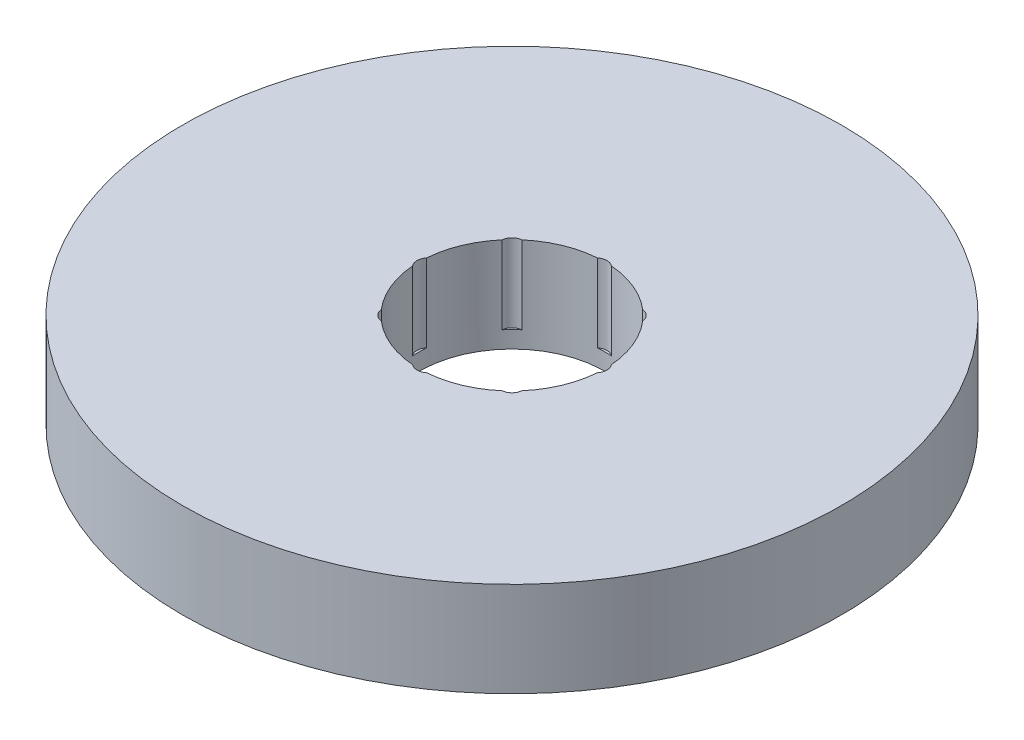
SolidWorks part; units mm, degrees
ref_plane "Front Plane" through (0, 0, 0) normal (0, 0, 1) x (1, 0, 0)
ref_plane "Top Plane" through (0, 0, 0) normal (0, 1, 0) x (1, 0, 0)
ref_plane "Right Plane" through (0, 0, 0) normal (1, 0, 0) x (0, 0, -1)
sketch "Sketch1" plane through (0, 0, 0) normal (0, 1, 0) x (1, 0, 0)
  circle A0 centre (0, 0) radius 80
  dimension "FLANGE_OD" = 160
extrude "Boss-Extrude1" add sketch "Sketch1" along normal blind 23
sketch "Sketch2" plane through (0, 0, 0) normal (0, 1, 0) x (1, 0, 0)
  circle A0 centre (0, 0) radius 22.5
  dimension "BORE_D" = 45
extrude "Cut-Extrude1" cut sketch "Sketch2" along normal through all
sketch "Sketch3" plane through (0, 23, 0) normal (0, 1, 0) x (1, 0, 0)
  circle A0 centre (0, 0) radius 20.3536 construction
  circle A1 centre (-20.3536, 0) radius 2.6855
  dimension "BOLT_D" = 5.371
  dimension "BOLT_PCD" = 40.7072
extrude "Cut-Extrude2" cut sketch "Sketch3" against normal blind 18.9106
pattern_circular "CirPattern1" count 8 over 360 about axis through (0, 0, 0) along (0, 1, 0) of "Cut-Extrude2"
